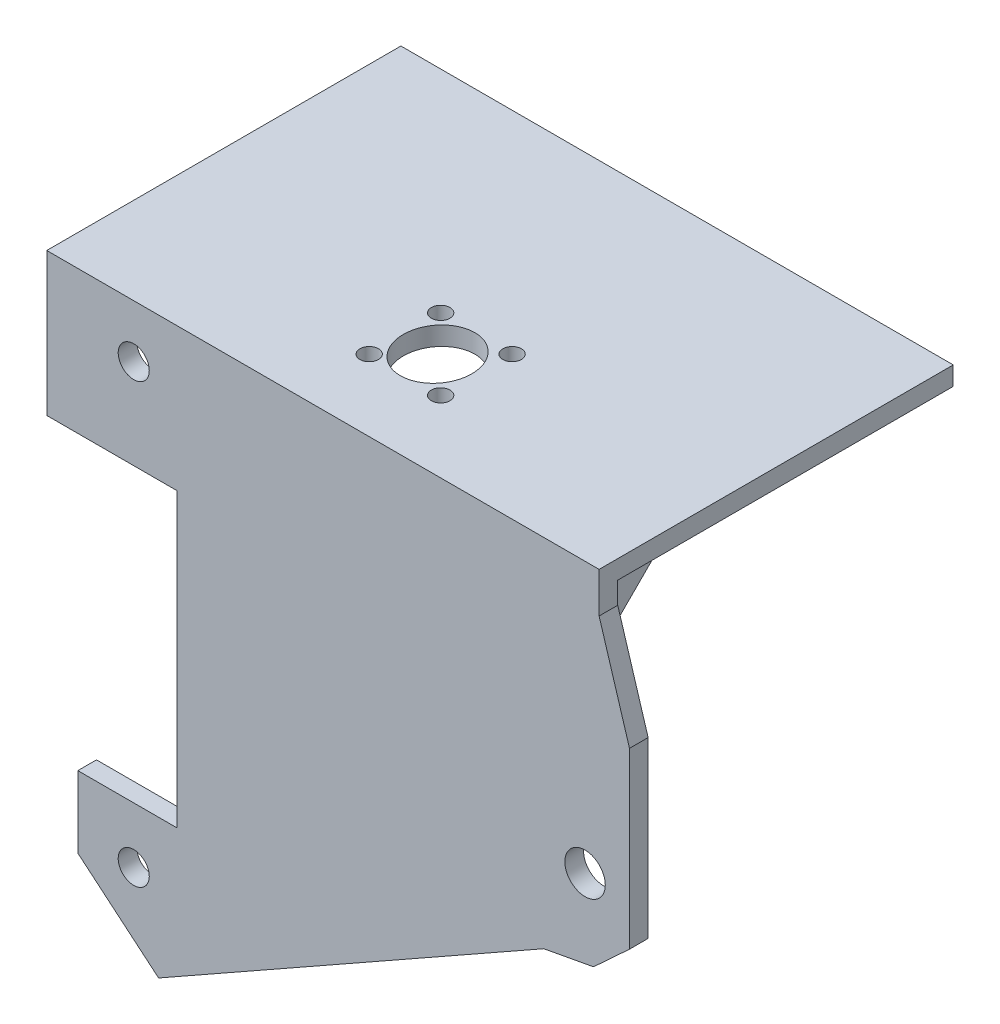
SolidWorks part; units mm, degrees
ref_plane "Front Plane" through (0, 0, 0) normal (0, 0, 1) x (1, 0, 0)
ref_plane "Top Plane" through (0, 0, 0) normal (0, 1, 0) x (1, 0, 0)
ref_plane "Right Plane" through (0, 0, 0) normal (1, 0, 0) x (0, 0, -1)
sketch "Sketch1" plane through (0, 0, 0) normal (0, 0, 1) x (1, 0, 0)
  line L0 (0, 0) -> (88.9, 0)
  line L1 (88.9, 0) -> (88.9, -3.5)
  line L2 (88.9, -3.5) -> (93.7917, -19.5)
  line L3 (93.7917, -19.5) -> (93.7917, -47.5)
  line L4 (0, 0) -> (0, -20)
  line L5 (0, -20) -> (21, -20)
  line L6 (21, -20) -> (21, -67)
  line L7 (21, -67) -> (5, -67)
  line L8 (5, -67) -> (5, -78.5)
  line L9 (5, -78.5) -> (18, -89.4083)
  line L10 (18, -89.4083) -> (80, -54.3304)
  line L11 (80, -54.3304) -> (88, -52.8477)
  line L12 (88, -52.8477) -> (93.7917, -47.5)
  dimension "D1" = 88.9
  dimension "D2" = 3.5
  dimension "D3" = 163
  dimension "D4" = 16
  dimension "D5" = 28
  dimension "D6" = 20
  dimension "D7" = 21
  dimension "D8" = 47
  dimension "D9" = 16
  dimension "D10" = 11.5
  dimension "D11" = 130
  dimension "D12" = 13
  dimension "D13" = 110.5
  dimension "D14" = 62
  dimension "D15" = 8
  dimension "D16" = 161
extrude "Boss-Extrude1" add sketch "Sketch1" along normal blind 3
sketch "Sketch2" plane through (0, 0, 0) normal (0, 1, 0) x (1, 0, 0)
  line L0 (45.8978, 14) -> (40.3978, 14) construction
  line L1 (0, -3) -> (88.9, -3)
  line L2 (0, -3) -> (0, 54)
  line L3 (0, 54) -> (88.9, 54)
  line L4 (88.9, -3) -> (88.9, 54)
  circle A0 centre (40.3978, 8.5) radius 1.5
  circle A1 centre (40.3978, 20) radius 1.5
  circle A2 centre (51.8978, 8.5) radius 1.5
  circle A3 centre (51.8978, 20) radius 1.5
  ellipse E0 centre (45.8978, 14) end of major axis (45.8978, 8) minor radius 5.5
  dimension "D9" = 3
  dimension "D10" = 3
  dimension "D11" = 3
  dimension "D12" = 3
  dimension "D1" = 88.9
  dimension "D2" = 57
  dimension "D3" = 45.8978
  dimension "D4" = 5.5
  dimension "D5" = 11.5
  dimension "D6" = 23
  dimension "D7" = 11.5
  dimension "D8" = 17
  dimension "D13" = 12
  dimension "D14" = 11
extrude "Boss-Extrude2" add sketch "Sketch2" along normal blind 3
ref_plane "Plane1" through (85.9, 0, 0) normal (1, 0, 0) x (0, 0, -1)
sketch "Sketch3" plane through (85.9, 0, 0) normal (1, 0, 0) x (0, 0, -1)
  line L0 (11.5, 0) -> (0, 0)
  line L1 (0, 0) -> (54, 0) construction
  line L2 (0, 0) -> (0, -11.5)
  line L3 (0, -19.5) -> (0, -3.5) construction
  line L4 (0, -11.5) -> (11.5, 0)
  dimension "D1" = 11.5
  dimension "D2" = 11.5
extrude "Boss-Extrude3" add sketch "Sketch3" against normal blind 84.5
sketch "Sketch4" plane through (0, 0, 0) normal (0, 0, -1) x (-1, 0, 0)
  line L0 (-1.4, -11.5) -> (-85.9, -11.5) construction
  line L1 (-81.4, -11.5) -> (-6.4, -11.5)
  line L2 (-81.4, -11.5) -> (-81.4, 0)
  line L3 (-81.4, 0) -> (-6.4, 0)
  line L4 (-6.4, -11.5) -> (-6.4, 0)
  line L5 (-50.8976, 0) -> (-85.9, 0) construction
  line L6 (-85.9, 13.7659) -> (-85.9, -13.7659) construction
  dimension "D1" = 75
  dimension "D2" = 4.5
extrude "Cut-Extrude2" cut sketch "Sketch4" along normal blind 84.5
sketch "Sketch6" plane through (0, 0, 3) normal (0, 0, 1) x (1, 0, 0)
  line L0 (0, 3) -> (0, -20) construction
  line L1 (0, 3) -> (88.9, 3) construction
  circle A0 centre (14, -76) radius 2.5
  circle A1 centre (86.644, -40.5) radius 3.25
  circle A2 centre (14, -5.5) radius 2.5
  dimension "D1" = 5
  dimension "D2" = 5
  dimension "D3" = 6.5
  dimension "D4" = 14
  dimension "D5" = 8.5
  dimension "D6" = 79
  dimension "D7" = 14
  dimension "D8" = 43.5
  dimension "D9" = 72.644
extrude "Cut-Extrude3" cut sketch "Sketch6" against normal blind 84.5
